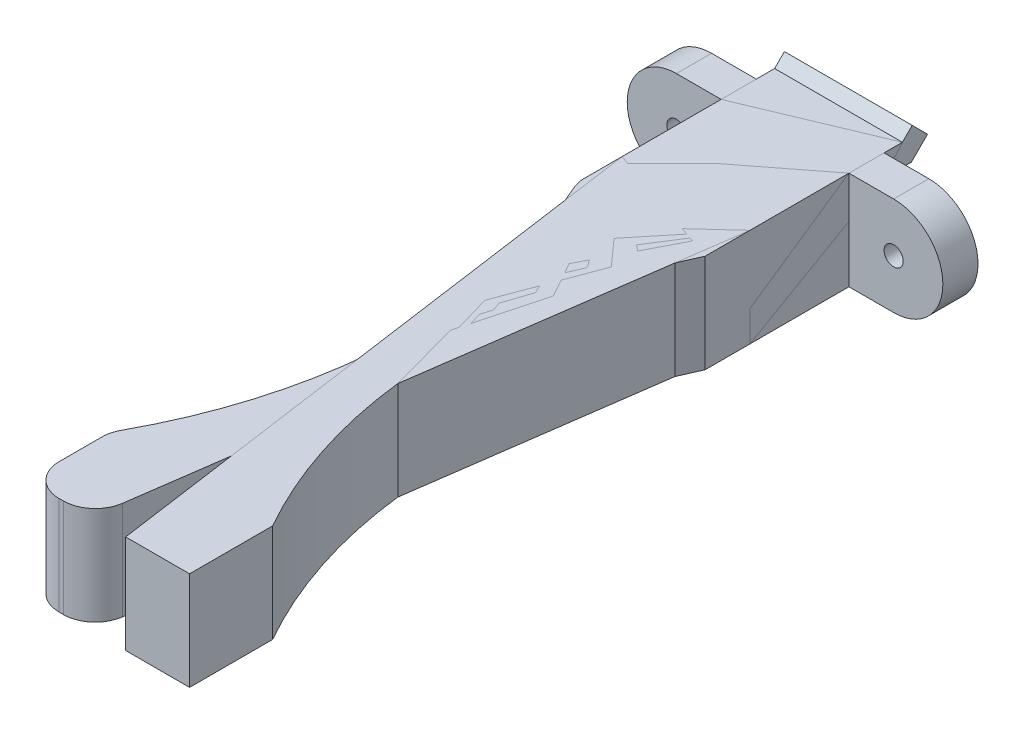
SolidWorks part; units mm, degrees
ref_plane "Front Plane" through (0, 0, 0) normal (0, 0, 1) x (1, 0, 0)
ref_plane "Top Plane" through (0, 0, 0) normal (0, 1, 0) x (1, 0, 0)
ref_plane "Right Plane" through (0, 0, 0) normal (1, 0, 0) x (0, 0, -1)
sketch "Sketch2" plane through (0, 0, 0) normal (0, 0, 1) x (1, 0, 0)
  line L0 (0, 5.9203) -> (0, 8.9503) construction
  line L1 (-5, -5.8182) -> (5, -5.8182)
  line L2 (-5, -5.8182) -> (-5, 8.9503)
  line L3 (-5, 8.9503) -> (5, 8.9503)
  line L4 (5, -5.8182) -> (5, 8.9503)
  line L7 (13.4766, 5.9203) -> (-18.5234, 5.9203) construction
  line L8 (0, -5.8182) -> (0, -2.7882) construction
  point P0 (0, 0)
  dimension "D1" = 10
extrude "Boss-Extrude1" add sketch "Sketch2" along normal blind 5
sketch "Sketch8" plane through (-5, 0, 0) normal (-1, 0, 0) x (0, 0, 1)
  line L6 (-0.15, 5.7703) -> (0, 5.7703)
  line L7 (0, 8.9503) -> (0, -5.8182) construction
  line L8 (0, 5.7703) -> (0, 4.0703)
  line L9 (0, 4.0703) -> (-0.15, 4.0703)
  line L11 (-0.15, -1.9297) -> (0, -1.9297)
  line L12 (-2.1379, 4.0703) -> (-0.15, 4.0703)
  line L13 (-0.15, 4.0703) -> (-0.15, 5.7703)
  line L14 (-0.15, 5.7703) -> (-1.4337, 5.7703)
  line L15 (-1.4337, 5.7703) -> (-2.2, 6.5366)
  line L16 (-2.2, 6.5366) -> (-3.4021, 5.3345)
  line L17 (-3.4021, 5.3345) -> (-2.1379, 4.0703)
  line L18 (-2.1379, 4.0703) -> (-0.15, 4.0703)
  line L20 (-0.15, 5.7703) -> (-1.4337, 5.7703)
  line L21 (-1.4337, 5.7703) -> (-2.2, 6.5366)
  line L22 (-2.2, 6.5366) -> (-3.4021, 5.3345)
  line L23 (-3.4021, 5.3345) -> (-2.1379, 4.0703)
  line L24 (-2.1379, -1.9297) -> (-0.15, -1.9297)
  line L25 (-0.15, -1.9297) -> (-0.15, -0.2297)
  line L26 (-0.15, -0.2297) -> (-1.4337, -0.2297)
  line L27 (-1.4337, -0.2297) -> (-2.2, 0.5366)
  line L28 (-2.2, 0.5366) -> (-3.4021, -0.6655)
  line L29 (-3.4021, -0.6655) -> (-2.1379, -1.9297)
  line L30 (-2.1379, -1.9297) -> (-0.15, -1.9297)
  line L32 (-0.15, -0.2297) -> (-1.4337, -0.2297)
  line L33 (-1.4337, -0.2297) -> (-2.2, 0.5366)
  line L34 (-2.2, 0.5366) -> (-3.4021, -0.6655)
  line L35 (-3.4021, -0.6655) -> (-2.1379, -1.9297)
  line L37 (-0.15, -0.2297) -> (0, -0.2297)
  line L38 (0, -1.9297) -> (0, -0.2297)
  dimension "D1" = 0.15
  dimension "D2" = 0.15
extrude "Boss-Extrude4" add sketch "Sketch8" against normal up to surface (10 mm away) up to face at (5, 1.566, 2.5)
sketch "Sketch9" plane through (0, 0, 0) normal (0, 0, -1) x (-1, 0, 0)
  line L4 (-5, 8.9503) -> (-5, 5.7703)
  line L5 (-5, 5.7703) -> (5, 5.7703)
  line L6 (5, 5.7703) -> (5, 8.9503)
  line L7 (5, 8.9503) -> (-5, 8.9503)
  line L8 (-5, 8.9503) -> (-5, 5.7703)
  line L10 (5, 5.7703) -> (5, 8.9503)
  line L11 (5, 8.9503) -> (-5, 8.9503)
  line L16 (5, -1.9297) -> (-5, -1.9297)
  line L17 (-5, -1.9297) -> (-5, -5.8182)
  line L18 (-5, -5.8182) -> (5, -5.8182)
  line L19 (5, -5.8182) -> (5, -1.9297)
  line L21 (-5, -1.9297) -> (-5, -5.8182)
  line L22 (-5, -5.8182) -> (5, -5.8182)
  line L23 (5, -5.8182) -> (5, -1.9297)
  line L26 (-5, 5.7703) -> (5, 5.7703)
  line L27 (5, -1.9297) -> (-5, -1.9297)
  dimension "D1" = 0
  dimension "D2" = 0
extrude "Cut-Extrude3" cut sketch "Sketch9" against normal blind 5
sketch "Sketch10" plane through (0, 5.7703, 0) normal (0, 1, 0) x (1, 0, 0)
  line L0 (-5, -5) -> (-5, -10.5)
  line L1 (-5, -10.5) -> (1.3524, -55.7)
  line L2 (1.3524, -55.7) -> (6.3524, -55.7)
  line L3 (-5, -5) -> (5, -5)
  line L4 (-120.9789, 453.7107) -> (412.3545, 453.7107) construction
  line L5 (6.3524, -55.7) -> (6.3524, -49.2)
  line L6 (5, -5) -> (5, -14)
  arc A1 (5, -14) -> (6.3524, -49.2) centre (39.6089, -30.2962) ccw
  dimension "D1" = 172
  dimension "D2" = 45.2
  dimension "D3" = 5
  dimension "D4" = 6.5
  dimension "D5" = 5.5
  dimension "D6" = 9
extrude "Boss-Extrude5" add sketch "Sketch10" against normal up to surface (7.7 mm away) up to face at (0, -1.9297, 1.4311)
ref_plane "Plane1" through (0, 0, 2.75) normal (0, 0, 1) x (1, 0, 0)
sketch "Sketch12" plane through (0, 0, 0) normal (0, 0, 1) x (1, 0, 0)
  line L0 (5, 5.7703) -> (8.5, 5.7703)
  line L1 (8.5, -1.9297) -> (5, -1.9297)
  line L2 (5, -1.9297) -> (5, 5.7703)
  line L3 (1.3524, 5.7703) -> (6.3524, 5.7703) construction
  line L4 (1.3524, -1.9297) -> (6.3524, -1.9297) construction
  line L5 (5, 5.3345) -> (5, 6.5366) construction
  line L6 (6.3524, 5.7703) -> (1.3552, 5.7703) construction
  arc A0 (8.5, 5.7703) -> (8.5, -1.9297) centre (8.5, 1.9203) cw
  circle A1 centre (8.5, 1.9203) radius 0.75
  dimension "D1" = 1.5
  dimension "D2" = 3.5
extrude "Boss-Extrude7" add sketch "Sketch12" along normal up to surface (2.75 mm away) up to plane "Plane1"
mirror "Mirror1" about plane through (0, 0, 0) normal (1, 0, 0) of bodies 112
fillet "Fillet1" radius 2.5 4 edges at (-5, 1.9203, 14) (-6.3524, 1.9203, 49.2) (-1.3524, 1.9203, 55.7) (-6.3524, 1.9203, 55.7)
